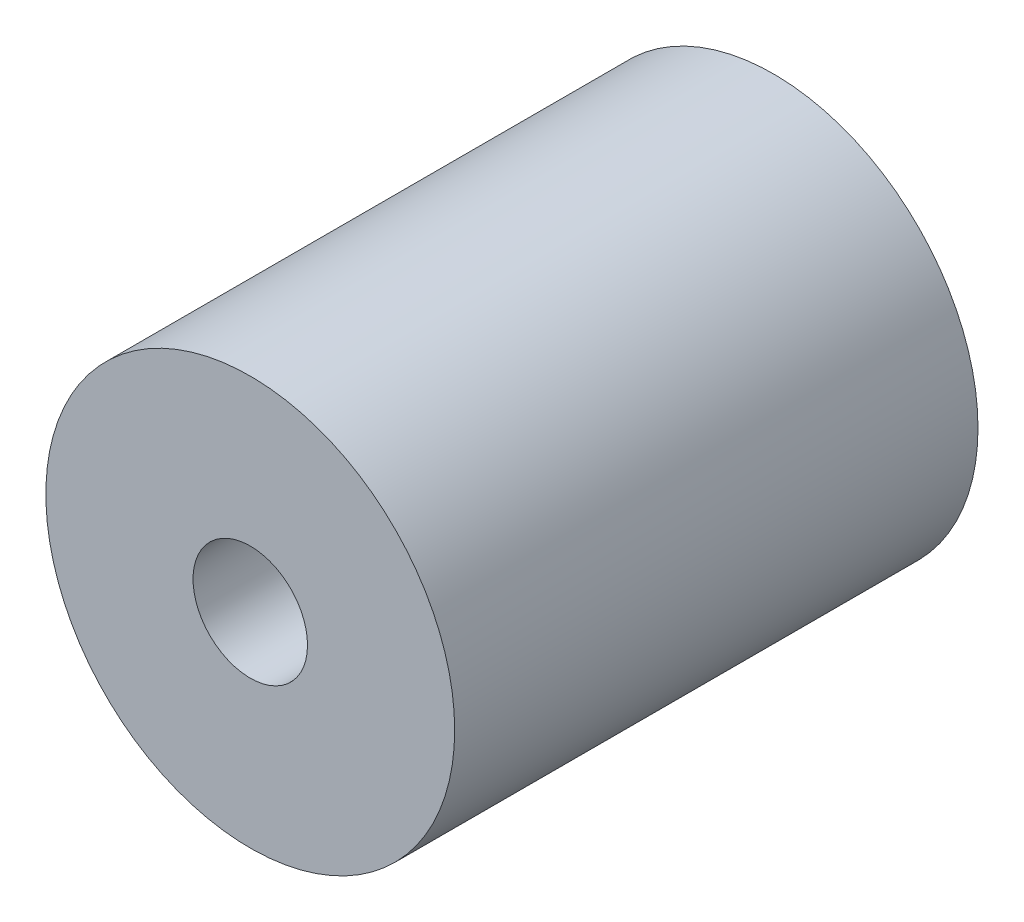
SolidWorks part; units mm, degrees
other "Title Block Table1"
other "DetailItem1"
material "PA Type 6 - Black"
ref_plane "Front Plane" through (0, 0, 0) normal (0, 0, 1) x (1, 0, 0)
ref_plane "Top Plane" through (0, 0, 0) normal (0, 1, 0) x (1, 0, 0)
ref_plane "Right Plane" through (0, 0, 0) normal (1, 0, 0) x (0, 0, -1)
ref_axis "X-Axis" through (-83.7009, 0, 0) along (1, 0, 0)
ref_axis "Y-Axis" through (0, 70.1691, 0) along (0, -1, 0)
ref_axis "Z-Axis" through (0, 0, -88.99) along (0, 0, 1)
sketch "Sketch1" plane through (0, 0, 0) normal (0, 0, 1) x (1, 0, 0)
  circle A0 centre (0, 0) radius 12.5
  circle A1 centre (0, 0) radius 3.5
  dimension "D1" = 25
  dimension "D2" = 7
extrude "Boss-Extrude1" add sketch "Sketch1" along normal mid plane 32
